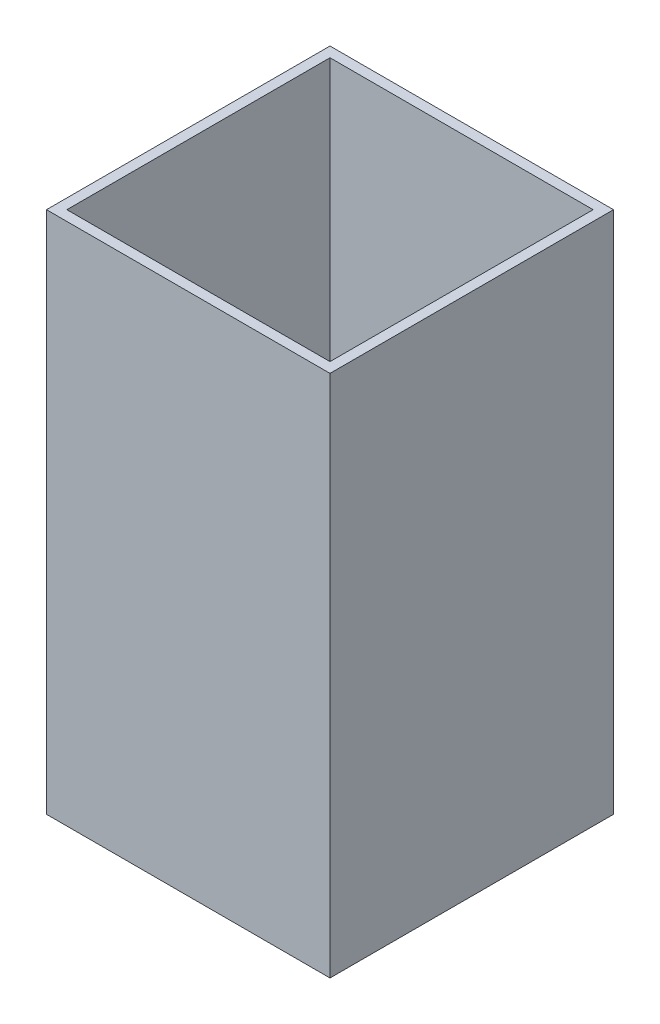
SolidWorks part; units mm, degrees
ref_plane "Front Plane" through (0, 0, 0) normal (0, 0, 1) x (1, 0, 0)
ref_plane "Top Plane" through (0, 0, 0) normal (0, 1, 0) x (1, 0, 0)
ref_plane "Right Plane" through (0, 0, 0) normal (1, 0, 0) x (0, 0, -1)
sketch "Sketch1" plane through (0, 0, 0) normal (0, 1, 0) x (1, 0, 0)
  line L1 (0, 0) -> (88.35, 0)
  line L2 (0, 0) -> (0, 88.35)
  line L3 (0, 88.35) -> (88.35, 88.35)
  line L4 (88.35, 0) -> (88.35, 88.35)
  line L5 (3.175, 3.175) -> (85.175, 3.175)
  line L6 (3.175, 3.175) -> (3.175, 85.175)
  line L7 (3.175, 85.175) -> (85.175, 85.175)
  line L8 (85.175, 3.175) -> (85.175, 85.175)
  line L9 (3.175, 85.175) -> (0, 85.175) construction
  line L10 (3.175, 85.175) -> (3.175, 88.35) construction
  line L11 (85.175, 3.175) -> (85.175, 0) construction
  line L12 (85.175, 3.175) -> (88.35, 3.175) construction
  dimension "D1" = 82
  dimension "D2" = 3.175
extrude "Boss-Extrude1" add sketch "Sketch1" along normal blind 160
sketch "Sketch2" plane through (0, 0, 0) normal (0, -1, 0) x (1, 0, 0)
  line L1 (0, 0) -> (88.35, 0)
  line L2 (0, 0) -> (0, -88.35)
  line L3 (0, -88.35) -> (88.35, -88.35)
  line L4 (88.35, 0) -> (88.35, -88.35)
extrude "Boss-Extrude2" add sketch "Sketch2" along normal blind 3.175
